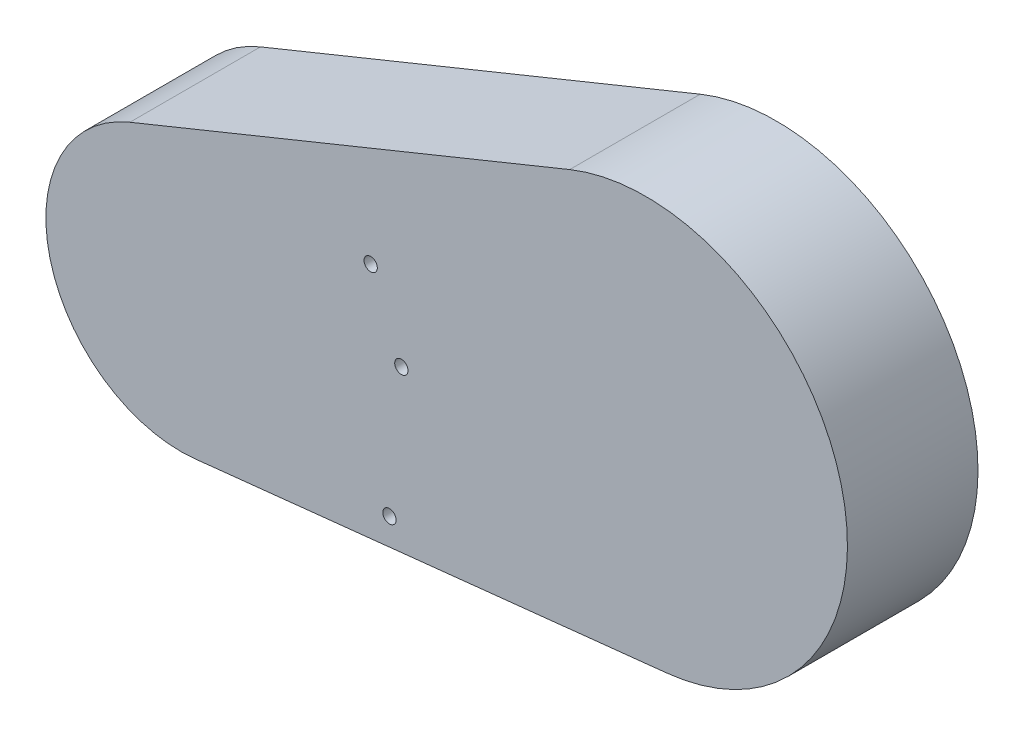
SolidWorks part; units mm, degrees
ref_plane "Front Plane" through (0, 0, 0) normal (0, 0, 1) x (1, 0, 0)
ref_plane "Top Plane" through (0, 0, 0) normal (0, 1, 0) x (1, 0, 0)
ref_plane "Right Plane" through (0, 0, 0) normal (1, 0, 0) x (0, 0, -1)
sketch "Sketch1" plane through (0, 0, 0) normal (0, 0, 1) x (1, 0, 0)
  line L0 (-196.7367, -55.8663) -> (-222.1367, -55.8663) construction
  line L1 (-246.406, 3.7881) -> (-36.314, 89.2603)
  line L2 (10.2328, -95.8196) -> (-215.2979, -119.9044)
  line L3 (-236.8343, -19.7394) -> (-26.7422, 65.7328) construction
  line L4 (8.4781, -70.4562) -> (-192.0771, -94.5892) construction
  line L5 (-213.1234, -20.4735) -> (-29.8155, 64.3971) construction
  line L6 (-217.9951, -94.648) -> (7.5356, -70.5632) construction
  line L7 (14.8118, -67.1357) -> (-211.32, -94.3464) construction
  line L8 (15.4187, -72.1793) -> (-210.7131, -99.39) construction
  line L9 (-184.0526, -93.5777) -> (7.8053, -73.0888) construction
  line L10 (-184.592, -88.5264) -> (7.2659, -68.0376) construction
  line L11 (-229.2044, -19.3775) -> (-25.785, 63.3801) construction
  line L12 (-231.1188, -14.672) -> (-27.6994, 68.0856) construction
  line L13 (-203.5832, -18.8555) -> (-28.7483, 62.0921) construction
  line L14 (-205.7175, -14.2456) -> (-30.8827, 66.702) construction
  line L15 (15.1153, -69.6575) -> (-211.0166, -96.8682) construction
  line L16 (-184.3223, -91.0521) -> (7.5356, -70.5632) construction
  line L17 (-204.6504, -16.5505) -> (-29.8155, 64.3971) construction
  line L18 (-230.1616, -17.0247) -> (-26.7422, 65.7328) construction
  circle A0 centre (-196.7367, -55.8663) radius 39.0022 construction
  circle A1 centre (-196.7367, -55.8663) radius 64.4022 construction
  arc A2 (-246.406, 3.7881) -> (-215.2979, -119.9044) centre (-222.1367, -55.8663) ccw
  circle A3 centre (0, 0) radius 70.9644 construction
  arc A4 (10.2328, -95.8196) -> (-36.314, 89.2603) centre (0, 0) ccw
  arc A5 (-157.7345, -55.8663) -> (-209.4367, 7.2713) centre (-222.1367, -55.8663) ccw construction
  arc A6 (-36.314, 89.2603) -> (10.2328, -95.8196) centre (0, 0) ccw construction
  circle A7 centre (0, 0) radius 96.3644 construction
  arc A8 (-209.4367, -119.0039) -> (-157.7345, -55.8663) centre (-222.1367, -55.8663) ccw construction
  arc A9 (-209.4367, 7.2713) -> (-246.406, 3.7881) centre (-222.1367, -55.8663) ccw construction
  arc A10 (-215.2979, -119.9044) -> (-209.4367, -119.0039) centre (-222.1367, -55.8663) ccw construction
  circle A11 centre (-131.3865, 2.594) radius 3.175
  circle A12 centre (-116.7292, -32.5753) radius 3.175
  circle A13 centre (-122.419, -97.2135) radius 3.175
  circle A14 centre (-222.1367, -55.8663) radius 107.95 construction
  circle A15 centre (-222.1367, -55.8663) radius 39.0022 construction
  dimension "D1" = 25.4
  dimension "D3" = 25.4
  dimension "D4" = 6.35
  dimension "D5" = 12.7
  dimension "D8" = 215.9
  dimension "D2" = 25.4
  dimension "D6" = 44.45
  dimension "D7" = 82.55
  dimension "D9" = 2.54
  dimension "D10" = 2.54
  dimension "D11" = 2.54
  dimension "D12" = 2.54
  dimension "D13" = 2.54
  dimension "D14" = 2.54
  dimension "D15" = 2.54
  dimension "D16" = 2.54
extrude "Boss-Extrude1" add sketch "Sketch1" along normal offset from surface (62.3697 mm away) 12.7 offset beyond the face yes
shell "Shell1" thickness 2.54 removed face at (-108.7581, -27.3521, 0)
sketch "Sketch2" plane through (0, 0, 0) normal (0, 1, 0) x (1, 0, 0)
  line L0 (-36.314, 0) -> (-246.406, 0) construction
  line L1 (-35.3568, 0) -> (-245.4488, 0) construction
  line L2 (-127, 0) -> (76.2, 0)
  arc A0 (-127, 0) -> (76.2, 0) centre (-25.4, 104.9192) ccw
  dimension "D1" = 146.05
  dimension "D2" = 203.2
  dimension "D3" = 127
extrude "Cut-Extrude1" [suppressed] cut sketch "Sketch2" along normal through all
